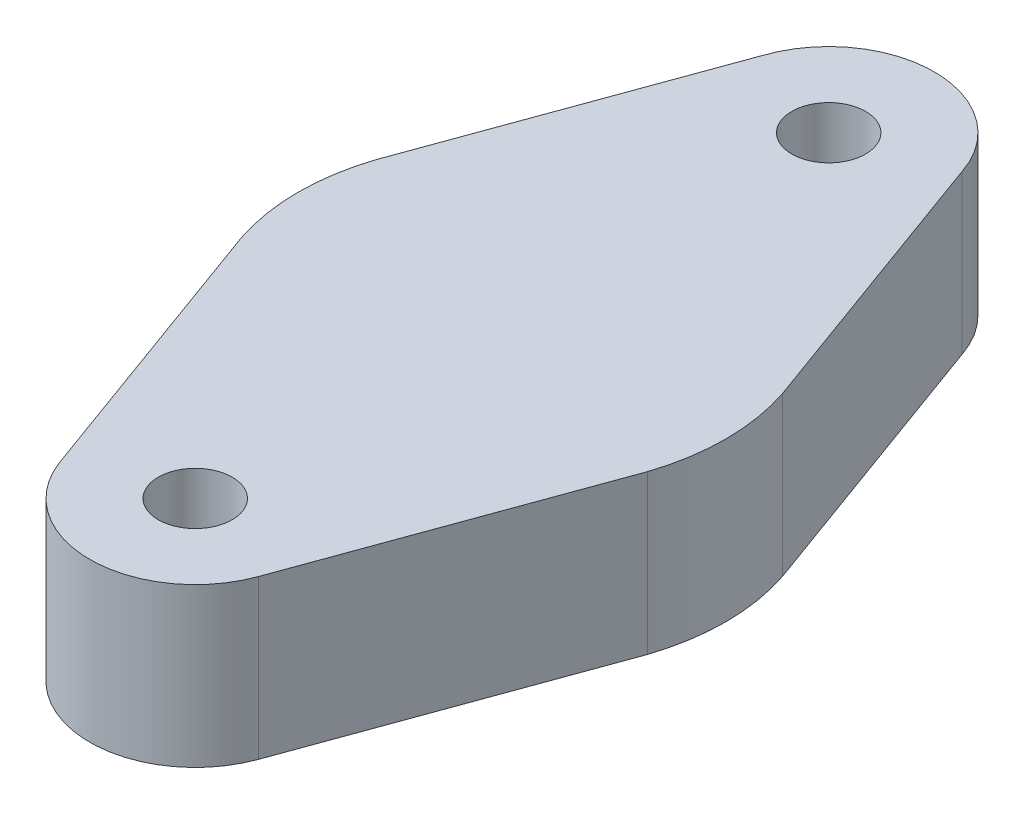
SolidWorks part; units mm, degrees
ref_plane "Спереди" through (0, 0, 0) normal (0, 0, 1) x (1, 0, 0)
ref_plane "Сверху" through (0, 0, 0) normal (0, 1, 0) x (1, 0, 0)
ref_plane "Справа" through (0, 0, 0) normal (1, 0, 0) x (0, 0, -1)
sketch "Эскиз1" plane through (0, 0, 0) normal (0, 1, 0) x (1, 0, 0)
  line L0 (0, 27.0868) -> (0, -27.7364) construction
  line L1 (-11.6506, 0) -> (13.5717, 0) construction
  line L2 (6.8277, 12) -> (-14.7219, 12) construction
  line L3 (6.418, -12) -> (-10.0515, -12) construction
  line L4 (7.6866, -2.5546) -> (3.7597, -13.3656)
  line L5 (7.6866, 2.5546) -> (3.7959, 13.2615)
  line L7 (-7.6866, 2.5546) -> (-3.7959, 13.2615)
  line L11 (-7.6866, -2.5546) -> (-3.7597, -13.3656)
  arc A0 (-7.6866, 2.5546) -> (-7.6866, -2.5546) centre (0, 0) ccw
  circle A1 centre (0, 12) radius 1.4
  circle A2 centre (0, -12) radius 1.4
  arc A11 (3.7959, 13.2615) -> (-3.7959, 13.2615) centre (0, 12) ccw
  arc A12 (-3.7597, -13.3656) -> (3.7597, -13.3656) centre (0, -12) ccw
  arc A16 (7.6866, -2.5546) -> (7.6866, 2.5546) centre (0, 0) ccw
  dimension "D1" = 16.2
  dimension "D2" = 2.8
  dimension "D3" = 2.8
  dimension "D4" = 12
  dimension "D5" = 12
  dimension "D6" = 8
  dimension "D7" = 8
extrude "Бобышка-Вытянуть1" add sketch "Эскиз1" along normal blind 6
